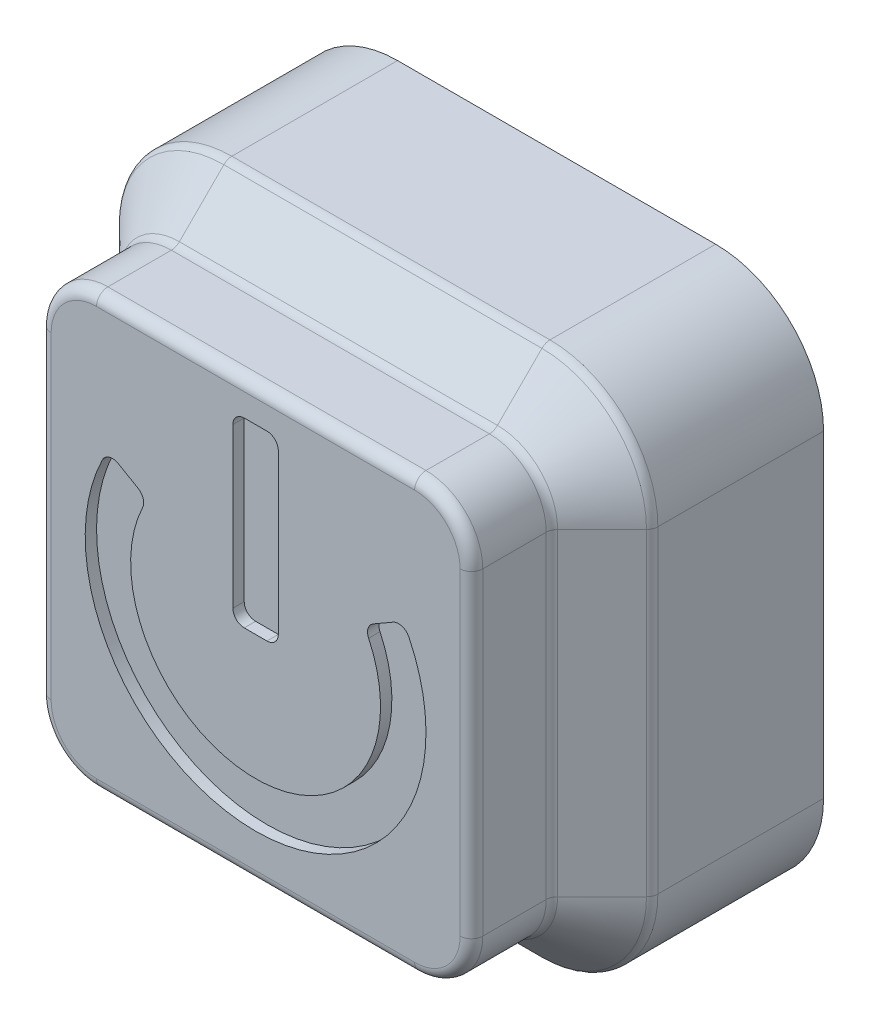
SolidWorks part; units mm, degrees
material "ABS"
ref_plane "前视基准面" through (0, 0, 0) normal (0, 0, 1) x (1, 0, 0)
ref_plane "上视基准面" through (0, 0, 0) normal (0, 1, 0) x (1, 0, 0)
ref_plane "右视基准面" through (0, 0, 0) normal (1, 0, 0) x (0, 0, -1)
other "Configuration Table"
sketch "草图1" plane through (0, 0, 0) normal (0, 0, 1) x (1, 0, 0)
  line L1 (-3.8, -3.8) -> (3.8, -3.8)
  line L2 (-3.8, -3.8) -> (-3.8, 3.8)
  line L3 (-3.8, 3.8) -> (3.8, 3.8)
  line L4 (3.8, -3.8) -> (3.8, 3.8)
  line L5 (-3.8, -3.8) -> (3.8, 3.8) construction
  line L6 (-3.8, 3.8) -> (3.8, -3.8) construction
  point P0 (0, 0)
  dimension "D1" = 7.6
extrude "凸台-拉伸1" add sketch "草图1" along normal blind 2.3
fillet "圆角1" radius 1 4 edges at (3.8, -3.8, 1.15) (-3.8, -3.8, 1.15) (-3.8, 3.8, 1.15) (3.8, 3.8, 1.15)
sketch "草图2" plane through (0, 0, 2.3) normal (0, 0, 1) x (1, 0, 0)
  line L0 (-3, 0) -> (3, 0)
  line L1 (-0.4, 3.2) -> (0.4, 3.2)
  line L2 (-0.4, 5.7) -> (0.4, 5.7)
  line L3 (-0.4, 5.7) -> (-0.4, -1.3)
  line L4 (-0.4, -1.3) -> (0.4, -1.3)
  line L5 (0.4, 5.7) -> (0.4, -1.3)
  line L6 (-0.4, 5.7) -> (0.4, -1.3) construction
  line L7 (-0.4, -1.3) -> (0.4, 5.7) construction
  line L8 (0, 0) -> (-2.5981, 1.5)
  line L9 (-2.5981, 1.5) -> (0, 0)
  line L10 (0, 0) -> (2.5981, 1.5)
  circle A0 centre (0, 0) radius 3
  circle A1 centre (0, 0) radius 2.2
  point P6 (0, 2.2)
  dimension "D1" = 0.8
  dimension "D2" = 6
  dimension "D3" = 0.8
  dimension "D4" = 7
  dimension "D5" = 4.5
  dimension "D6" = 30
  dimension "D7" = 30
extrude "切除-拉伸1" cut sketch "草图2" against normal blind 0.2 contours A0 L5 L1 L3 | A1 L5 A0 L3 | L5 A1 L3 L8 L10 | A1 L9 A0 L0 | A1 L0 A0 | A1 L0 A0 L10 | L0 L8 L3 | L10 L0 L5 region at (2.5024, 0.6705, 2.3) region at (2.6, -0.0671, 2.3) region at (0.2667, 0.077, 2.3) region at (-2.5024, 0.6705, 2.3) region at (-0.2667, 0.077, 2.3) region at (0, 1.1506, 2.3) region at (0, 2.5894, 2.3) region at (0, 3.0954, 2.3)
fillet "圆角2" radius 0.2 8 edges at (0.4, 0, 2.2) (0.4, 3.2, 2.2) (-0.4, 0, 2.2) (-0.4, 3.2, 2.2) (-1.9053, 1.1, 2.2) (2.5981, 1.5, 2.2) (1.9053, 1.1, 2.2) (-2.5981, 1.5, 2.2)
sketch "草图3" plane through (0, 0, 0) normal (0, 0, -1) x (-1, 0, 0)
  line L0 (-3.3, 2.8) -> (-3.3, -2.8)
  line L1 (-2.8, -3.3) -> (2.8, -3.3)
  line L2 (3.3, -2.8) -> (3.3, 2.8)
  line L3 (2.8, 3.3) -> (-2.8, 3.3)
  line L4 (-3.8, 2.8) -> (-3.8, -2.8)
  line L5 (-2.8, -3.8) -> (2.8, -3.8)
  line L6 (3.8, -2.8) -> (3.8, 2.8)
  line L7 (2.8, 3.8) -> (-2.8, 3.8)
  line L8 (-3.8, 2.8) -> (-3.8, -2.8)
  line L9 (-2.8, -3.8) -> (2.8, -3.8)
  line L10 (3.8, -2.8) -> (3.8, 2.8)
  line L11 (2.8, 3.8) -> (-2.8, 3.8)
  line L12 (2.8, 4.7) -> (-2.8, 4.7)
  line L13 (-4.7, 2.8) -> (-4.7, -2.8)
  line L14 (-2.8, -4.7) -> (2.8, -4.7)
  line L15 (4.7, -2.8) -> (4.7, 2.8)
  arc A0 (-2.8, 3.3) -> (-3.3, 2.8) centre (-2.8, 2.8) ccw
  arc A1 (-3.3, -2.8) -> (-2.8, -3.3) centre (-2.8, -2.8) ccw
  arc A2 (2.8, -3.3) -> (3.3, -2.8) centre (2.8, -2.8) ccw
  arc A3 (3.3, 2.8) -> (2.8, 3.3) centre (2.8, 2.8) ccw
  arc A4 (-3.8, -2.8) -> (-2.8, -3.8) centre (-2.8, -2.8) ccw
  arc A5 (2.8, -3.8) -> (3.8, -2.8) centre (2.8, -2.8) ccw
  arc A6 (3.8, 2.8) -> (2.8, 3.8) centre (2.8, 2.8) ccw
  arc A7 (-2.8, 3.8) -> (-3.8, 2.8) centre (-2.8, 2.8) ccw
  arc A8 (-3.8, -2.8) -> (-2.8, -3.8) centre (-2.8, -2.8) ccw
  arc A9 (2.8, -3.8) -> (3.8, -2.8) centre (2.8, -2.8) ccw
  arc A10 (3.8, 2.8) -> (2.8, 3.8) centre (2.8, 2.8) ccw
  arc A11 (-2.8, 3.8) -> (-3.8, 2.8) centre (-2.8, 2.8) ccw
  arc A12 (-2.8, 4.7) -> (-4.7, 2.8) centre (-2.8, 2.8) ccw
  arc A13 (-4.7, -2.8) -> (-2.8, -4.7) centre (-2.8, -2.8) ccw
  arc A14 (2.8, -4.7) -> (4.7, -2.8) centre (2.8, -2.8) ccw
  arc A15 (4.7, 2.8) -> (2.8, 4.7) centre (2.8, 2.8) ccw
  line M17 (-3.8, 2.8) -> (-3.8, -2.8)
  arc M18 (-3.8, -2.8) -> (-2.8, -3.8) centre (-2.8, -2.8) ccw
  line M19 (-2.8, -3.8) -> (2.8, -3.8)
  arc M20 (2.8, -3.8) -> (3.8, -2.8) centre (2.8, -2.8) ccw
  line M21 (3.8, -2.8) -> (3.8, 2.8)
  arc M22 (3.8, 2.8) -> (2.8, 3.8) centre (2.8, 2.8) ccw
  line M23 (2.8, 3.8) -> (-2.8, 3.8)
  arc M24 (-2.8, 3.8) -> (-3.8, 2.8) centre (-2.8, 2.8) ccw
  dimension "D1" = 0
  dimension "D2" = 0.5
  dimension "D3" = 0.9
extrude "凸台-拉伸2" add sketch "草图3" along normal blind 3 and the other way blind 1 contours L15 A15 L12 A12 L13 A13 L14 A14 M17 M24 M23 M22 M21 M20 M19 M18 | A3 L2 A2 L1 A1 L0 A0 L3 M24 M17 M18 M19 M20 M21 M22 M23 region at (3.4311, 3.4311, 0) region at (-4.0495, 4.0495, 0)
chamfer "倒角1" distance 1 angle 45 8 edges at (0, -3.3, -3) (-3.1536, -3.1536, -3) (3.1536, -3.1536, -3) (-3.3, 0, -3) (3.3, 0, -3) (-3.1536, 3.1536, -3) (3.1536, 3.1536, -3) (0, 3.3, -3)
chamfer "倒角2" distance 1 angle 45 8 edges at (4.7, 0, 1) (4.1435, -4.1435, 1) (4.1435, 4.1435, 1) (0, -4.7, 1) (0, 4.7, 1) (-4.1435, -4.1435, 1) (-4.1435, 4.1435, 1) (-4.7, 0, 1)
fillet "圆角3" radius 0.2 16 edges at (3.5071, 3.5071, 0.9) (3.8, 0, 0.9) (3.5071, -3.5071, 0.9) (0, -3.8, 0.9) (-3.5071, -3.5071, 0.9) (-3.8, 0, 0.9) (-3.5071, 3.5071, 0.9) (4.1435, 4.1435, 0) (0, 4.7, 0) (-4.1435, 4.1435, 0) (-4.7, 0, 0) (-4.1435, -4.1435, 0) (0, -4.7, 0) (4.1435, -4.1435, 0) (0, 3.8, 0.9) (4.7, 0, 0)
fillet "圆角4" radius 0.2 8 edges at (-3.5071, -3.5071, 2.3) (-3.8, 0, 2.3) (-3.5071, 3.5071, 2.3) (0, 3.8, 2.3) (3.5071, 3.5071, 2.3) (3.8, 0, 2.3) (3.5071, -3.5071, 2.3) (0, -3.8, 2.3)
sketch "草图4" plane through (0, 0, 0) normal (0, 0, -1) x (-1, 0, 0)
  circle A0 centre (0, 0) radius 2.4
  dimension "D1" = 4.8
extrude "凸台-拉伸3" add sketch "草图4" along normal blind 1.8
fillet "圆角5" radius 0.5 10 edges at (-3.1536, -3.1536, 0) (0, -3.3, 0) (3.1536, -3.1536, 0) (3.3, 0, 0) (3.1536, 3.1536, 0) (0, 3.3, 0) (-3.1536, 3.1536, 0) (-3.3, 0, 0) (-2.4, 0, 0) (-2.4, 0, -1.8)
